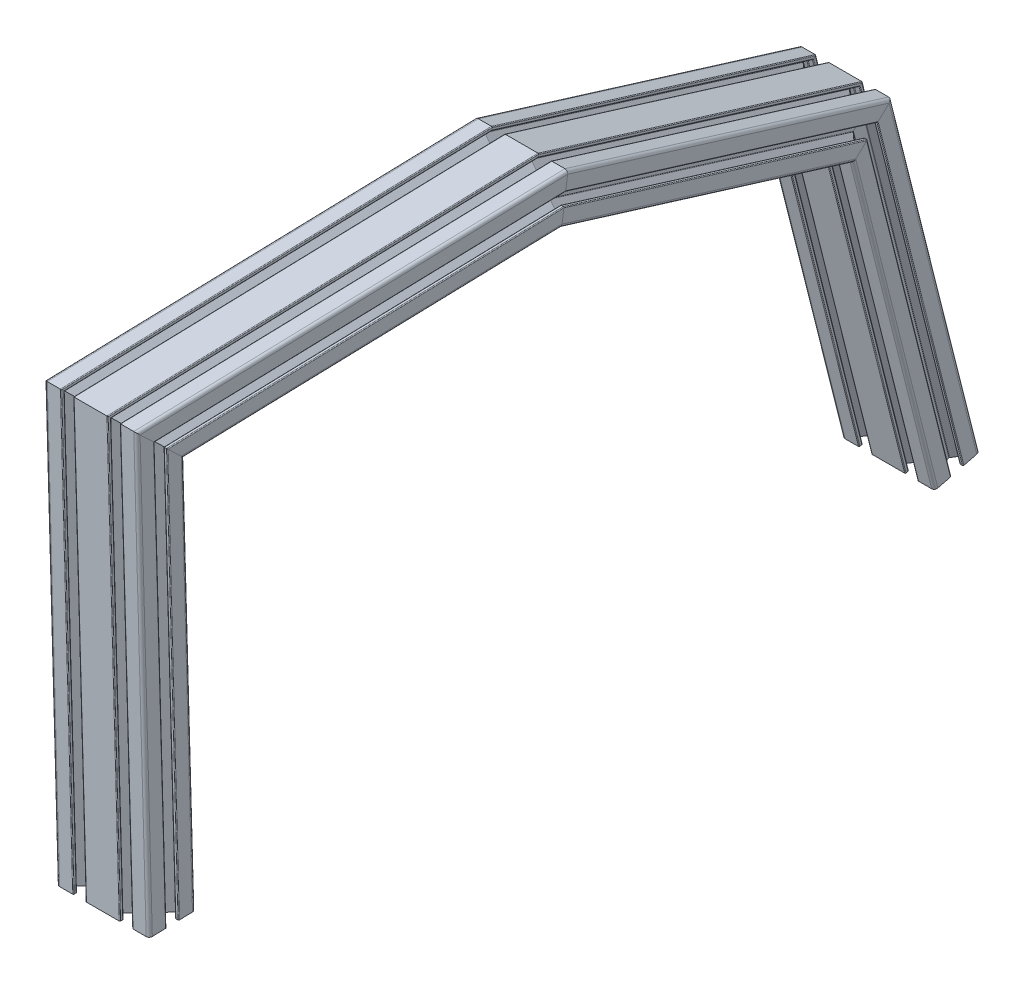
SolidWorks part; units mm, degrees
ref_plane "Front Plane" through (0, 0, 0) normal (0, 0, 1) x (1, 0, 0)
ref_plane "Top Plane" through (0, 0, 0) normal (0, 1, 0) x (1, 0, 0)
ref_plane "Right Plane" through (0, 0, 0) normal (1, 0, 0) x (0, 0, -1)
sketch "Sketch2" plane through (66.7101, 0, 48.5855) normal (0, 1, 0) x (1, 0, 0)
  line L1 (-190.5, -254) -> (190.5, -254)
  line L2 (-190.5, -254) -> (-190.5, 254)
  line L3 (-190.5, 254) -> (190.5, 254)
  line L4 (190.5, -254) -> (190.5, 254)
  line L5 (-190.5, -254) -> (190.5, 254) construction
  line L6 (-190.5, 254) -> (190.5, -254) construction
  point P0 (0, 0)
sketch "Sketch3" plane through (0, 0, 0) normal (0, 1, 0) x (1, 0, 0)
  line L0 (66.7101, -48.5855) -> (66.7101, -302.5855) construction
  line L1 (66.7101, -302.5855) -> (66.7101, 205.4145) construction
  line L2 (-123.7899, -302.5855) -> (257.2101, -302.5855) construction
  line L10 (-123.7899, 205.4145) -> (257.2101, 205.4145) construction
  point P3 (0, 0)
  point P7 (0, 0)
  point P8 (0, 0)
  point P9 (0, 0)
  point P13 (0, 0)
  point P14 (0, 0)
  point P16 (66.7101, 205.4145)
ref_plane "Plane1" through (66.7101, 0, 0) normal (1, 0, 0) x (0, 0, -1)
sketch "Sketch5" plane through (66.7101, 0, 0) normal (1, 0, 0) x (0, 0, -1)
  line L0 (-48.5855, 0) -> (-48.5855, 279.4) construction
  line L1 (-302.5855, 0) -> (-310.1662, 272.1127)
  line L2 (-302.5855, 0) -> (205.4145, 0) construction
  line L3 (-302.5855, 0) -> (205.4145, 0) construction
  line L4 (-310.1662, 272.1127) -> (-48.5855, 279.4)
  line L5 (-48.5855, 279.4) -> (150.4939, 218.0588)
  line L6 (150.4939, 218.0588) -> (205.4145, 0)
  point P10 (0, 0)
  point P28 (205.4145, 0)
  dimension "D1" = 279.4
other "8020 6030(1)" corner treatment miter
ref_plane "Plane2" through (66.7101, 0, 302.5855) normal (0, -0.9996, -0.0278) x (1, 0, 0)
sketch "Sketch21" plane through (66.7101, 0, 302.5855) normal (0, -0.9996, -0.0278) x (1, 0, 0)
  line L0 (11.1749, 2.3185) -> (11.9567, 1.3394) construction
  line L1 (13.6606, 3.0433) -> (12.6815, 3.8251) construction
  line L2 (-4.55, 12.3) -> (-4.55, 9.2682)
  line L3 (4.05, 12.8) -> (-4.05, 12.8)
  line L4 (4.55, 9.2682) -> (4.55, 12.3)
  line L5 (9.0188, 4.178) -> (4.9893, 8.2075)
  line L6 (9.1653, 0.8875) -> (9.1653, 3.8245)
  line L7 (9.6753, -0.0625) -> (9.1653, 0.8875) construction
  line L8 (9.1653, -1.0125) -> (9.6753, -0.0625) construction
  line L9 (9.1653, -3.8245) -> (9.1653, -1.0125)
  line L10 (4.9893, -8.2075) -> (9.0188, -4.178)
  line L11 (4.55, -12.3) -> (4.55, -9.2682)
  line L12 (-4.05, -12.8) -> (4.05, -12.8)
  line L13 (-4.55, -9.2682) -> (-4.55, -12.3)
  line L14 (-9.0188, -4.178) -> (-4.9893, -8.2075)
  line L15 (-9.1653, -1.0125) -> (-9.1653, -3.8245)
  line L16 (-9.6753, -0.0625) -> (-9.1653, -1.0125) construction
  line L17 (-9.1653, 0.8875) -> (-9.6753, -0.0625) construction
  line L18 (-9.1653, 3.8245) -> (-9.1653, 0.8875)
  line L19 (-4.9893, 8.2075) -> (-9.0188, 4.178)
  line L20 (17.3185, 3.8251) -> (16.3393, 3.0433) construction
  line L21 (18.0433, 1.3394) -> (18.8251, 2.3185) construction
  line L22 (18.8251, -2.3185) -> (18.0433, -1.3394) construction
  line L23 (16.3393, -3.0433) -> (17.3185, -3.8251) construction
  line L24 (12.6856, -3.8343) -> (13.6707, -3.0477) construction
  line L25 (11.9608, -1.3486) -> (11.179, -2.3278) construction
  line L26 (-18.8251, 2.3185) -> (-18.0433, 1.3394) construction
  line L27 (-16.3393, 3.0433) -> (-17.3185, 3.8251) construction
  line L28 (-12.6815, 3.8251) -> (-13.6606, 3.0433) construction
  line L29 (-11.9567, 1.3394) -> (-11.1749, 2.3185) construction
  line L30 (-11.1749, -2.3185) -> (-11.9567, -1.3394) construction
  line L31 (-13.6606, -3.0433) -> (-12.6815, -3.8251) construction
  line L32 (-17.3144, -3.8343) -> (-16.3292, -3.0477) construction
  line L33 (-18.0392, -1.3486) -> (-18.821, -2.3278) construction
  line L34 (-24.5, 9.88) -> (-24.5, 13.319)
  line L35 (-28.3189, 9.5) -> (-24.88, 9.5)
  line L36 (-28.6999, 12.7) -> (-28.6999, 9.881)
  line L37 (-24.881, 13.7) -> (-27.6999, 13.7)
  line L38 (-7.2674, -12.7425) -> (-10.4375, -12.7425)
  line L39 (-10.9375, -13.2425) -> (-10.9375, -14.5)
  line L40 (-10.4375, -15) -> (10.4375, -15)
  line L41 (10.9375, -14.5) -> (10.9375, -13.2425)
  line L42 (10.4375, -12.7425) -> (7.2674, -12.7425)
  line L43 (6.75, -12.2428) -> (6.75, -10.2602)
  line L44 (6.8964, -9.9067) -> (10.822, -5.9811)
  line L45 (11.1755, -5.8347) -> (14.05, -5.8347)
  line L46 (14.05, -5.8347) -> (15, -5.3247) construction
  line L47 (15, -5.3247) -> (15.95, -5.8347) construction
  line L48 (15.95, -5.8347) -> (18.8244, -5.8347)
  line L49 (19.178, -5.9811) -> (23.1035, -9.9067)
  line L50 (23.25, -10.2602) -> (23.25, -12.2428)
  line L51 (22.7325, -12.7425) -> (19.4375, -12.7425)
  line L52 (18.9375, -13.2425) -> (18.9375, -14.5)
  line L53 (19.4375, -15) -> (27.9999, -15)
  line L54 (29.9999, -13) -> (29.9999, -4.5625)
  line L55 (29.4999, -4.0625) -> (28.2425, -4.0625)
  line L56 (27.7425, -4.5625) -> (27.7425, -7.7325)
  line L57 (27.2428, -8.25) -> (25.2602, -8.25)
  line L58 (24.9066, -8.1035) -> (20.9811, -4.178)
  line L59 (20.8347, -3.8245) -> (20.8347, -1.0125)
  line L60 (20.8347, -1.0125) -> (20.3247, -0.0625) construction
  line L61 (20.3247, -0.0625) -> (20.8347, 0.8875) construction
  line L62 (20.8347, 0.8875) -> (20.8347, 3.8245)
  line L63 (20.9811, 4.178) -> (24.9066, 8.1035)
  line L64 (25.2602, 8.25) -> (27.2428, 8.25)
  line L65 (27.7425, 7.7325) -> (27.7425, 4.4375)
  line L66 (28.2425, 3.9375) -> (29.4999, 3.9375)
  line L67 (29.9999, 4.4375) -> (29.9999, 13)
  line L68 (27.9999, 15) -> (19.5625, 15)
  line L69 (19.0625, 14.5) -> (19.0625, 13.2425)
  line L70 (19.5625, 12.7425) -> (22.7325, 12.7425)
  line L71 (23.25, 12.2428) -> (23.25, 10.2602)
  line L72 (23.1035, 9.9067) -> (19.178, 5.9811)
  line L73 (18.8244, 5.8347) -> (15.95, 5.8347)
  line L74 (15.95, 5.8347) -> (15, 5.3247) construction
  line L75 (15, 5.3247) -> (14.05, 5.8347) construction
  line L76 (14.05, 5.8347) -> (11.1755, 5.8347)
  line L77 (10.822, 5.9811) -> (6.8964, 9.9067)
  line L78 (6.75, 10.2602) -> (6.75, 12.2428)
  line L79 (7.2674, 12.7425) -> (10.5625, 12.7425)
  line L80 (11.0625, 13.2425) -> (11.0625, 14.5)
  line L81 (10.5625, 15) -> (-10.5625, 15)
  line L82 (-11.0625, 14.5) -> (-11.0625, 13.2425)
  line L83 (-10.5625, 12.7425) -> (-7.2674, 12.7425)
  line L84 (-6.75, 12.2428) -> (-6.75, 10.2602)
  line L85 (-6.8964, 9.9067) -> (-10.822, 5.9811)
  line L86 (-11.1755, 5.8347) -> (-14.05, 5.8347)
  line L87 (-14.05, 5.8347) -> (-15, 5.3247) construction
  line L88 (-15, 5.3247) -> (-15.95, 5.8347) construction
  line L89 (-15.95, 5.8347) -> (-18.8244, 5.8347)
  line L90 (-19.178, 5.9811) -> (-23.1035, 9.9067)
  line L91 (-23.25, 10.2602) -> (-23.25, 12.2428)
  line L92 (-22.7325, 12.7425) -> (-19.5625, 12.7425)
  line L93 (-19.0625, 13.2425) -> (-19.0625, 14.5)
  line L94 (-19.5625, 15) -> (-27.9999, 15)
  line L95 (-29.9999, 13) -> (-29.9999, 4.4375)
  line L96 (-29.4999, 3.9375) -> (-28.2425, 3.9375)
  line L97 (-27.7425, 4.4375) -> (-27.7425, 7.7325)
  line L98 (-27.2428, 8.25) -> (-25.2602, 8.25)
  line L99 (-24.9066, 8.1035) -> (-20.9811, 4.178)
  line L100 (-20.8347, 3.8245) -> (-20.8347, 0.8875)
  line L101 (-20.8347, 0.8875) -> (-20.3247, -0.0625) construction
  line L102 (-20.3247, -0.0625) -> (-20.8347, -1.0125) construction
  line L103 (-20.8347, -1.0125) -> (-20.8347, -3.8245)
  line L104 (-20.9811, -4.178) -> (-24.9066, -8.1035)
  line L105 (-25.2602, -8.25) -> (-27.2428, -8.25)
  line L106 (-27.7425, -7.7325) -> (-27.7425, -4.5625)
  line L107 (-28.2425, -4.0625) -> (-29.4999, -4.0625)
  line L108 (-29.9999, -4.5625) -> (-29.9999, -13)
  line L109 (-27.9999, -15) -> (-19.4375, -15)
  line L110 (-18.9375, -14.5) -> (-18.9375, -13.2425)
  line L111 (-19.4375, -12.7425) -> (-22.7325, -12.7425)
  line L112 (-23.25, -12.2428) -> (-23.25, -10.2602)
  line L113 (-23.1035, -9.9067) -> (-19.178, -5.9811)
  line L114 (-18.8244, -5.8347) -> (-15.95, -5.8347)
  line L115 (-15.95, -5.8347) -> (-15, -5.3247) construction
  line L116 (-15, -5.3247) -> (-14.05, -5.8347) construction
  line L117 (-14.05, -5.8347) -> (-11.1755, -5.8347)
  line L118 (-10.822, -5.9811) -> (-6.8964, -9.9067)
  line L119 (-6.75, -10.2602) -> (-6.75, -12.2428)
  line L120 (-24.88, -9.5) -> (-28.3189, -9.5)
  line L121 (-24.5, -13.319) -> (-24.5, -9.88)
  line L122 (-27.6999, -13.7) -> (-24.881, -13.7)
  line L123 (-28.6999, -9.881) -> (-28.6999, -12.7)
  line L124 (24.5, -9.88) -> (24.5, -13.319)
  line L125 (28.3189, -9.5) -> (24.88, -9.5)
  line L126 (28.6999, -12.7) -> (28.6999, -9.881)
  line L127 (24.881, -13.7) -> (27.6999, -13.7)
  line L128 (27.6999, 13.7) -> (24.881, 13.7)
  line L129 (28.6999, 9.881) -> (28.6999, 12.7)
  line L130 (24.88, 9.5) -> (28.3189, 9.5)
  line L131 (24.5, 13.319) -> (24.5, 9.88)
  line L132 (-14.05, 5.8347) -> (-15.95, 5.8347)
  line L133 (-20.8347, 0.8875) -> (-20.8347, -1.0125)
  line L134 (-15.95, -5.8347) -> (-14.05, -5.8347)
  line L135 (-9.1653, -1.0125) -> (-9.1653, 0.8875)
  line L136 (9.1653, 0.8875) -> (9.1653, -1.0125)
  line L137 (14.05, -5.8347) -> (15.95, -5.8347)
  line L138 (20.8347, -1.0125) -> (20.8347, 0.8875)
  line L139 (15.95, 5.8347) -> (14.05, 5.8347)
  arc A0 (-4.05, 12.8) -> (-4.55, 12.3) centre (-4.05, 12.3) ccw
  arc A1 (4.55, 12.3) -> (4.05, 12.8) centre (4.05, 12.3) ccw
  arc A2 (4.55, 9.2682) -> (4.9893, 8.2075) centre (6.05, 9.2682) ccw
  arc A3 (9.1653, 3.8245) -> (9.0188, 4.178) centre (8.6653, 3.8245) ccw
  arc A4 (9.0188, -4.178) -> (9.1653, -3.8245) centre (8.6653, -3.8245) ccw
  arc A5 (4.9893, -8.2075) -> (4.55, -9.2682) centre (6.05, -9.2682) ccw
  arc A6 (4.05, -12.8) -> (4.55, -12.3) centre (4.05, -12.3) ccw
  arc A7 (-4.55, -12.3) -> (-4.05, -12.8) centre (-4.05, -12.3) ccw
  arc A8 (-4.55, -9.2682) -> (-4.9893, -8.2075) centre (-6.05, -9.2682) ccw
  arc A9 (-9.1653, -3.8245) -> (-9.0188, -4.178) centre (-8.6653, -3.8245) ccw
  arc A10 (-9.0188, 4.178) -> (-9.1653, 3.8245) centre (-8.6653, 3.8245) ccw
  arc A11 (-4.9893, 8.2075) -> (-4.55, 9.2682) centre (-6.05, 9.2682) ccw
  arc A12 (12.6815, 3.8251) -> (11.1749, 2.3185) centre (12.0126, 2.9874) ccw construction
  arc A13 (16.3393, 3.0433) -> (13.6606, 3.0433) centre (15, 0) ccw construction
  arc A14 (18.8251, 2.3185) -> (17.3185, 3.8251) centre (17.9873, 2.9874) ccw construction
  arc A15 (18.0433, -1.3394) -> (18.0433, 1.3394) centre (15, 0) ccw construction
  arc A16 (17.3185, -3.8251) -> (18.8251, -2.3185) centre (17.9873, -2.9874) ccw construction
  arc A17 (13.6707, -3.0477) -> (16.3393, -3.0433) centre (15, 0) ccw construction
  arc A18 (11.179, -2.3278) -> (12.6856, -3.8343) centre (12.0167, -2.9966) ccw construction
  arc A19 (11.9567, 1.3394) -> (11.9608, -1.3486) centre (15, 0) ccw construction
  arc A20 (-17.3185, 3.8251) -> (-18.8251, 2.3185) centre (-17.9873, 2.9874) ccw construction
  arc A21 (-13.6606, 3.0433) -> (-16.3393, 3.0433) centre (-15, 0) ccw construction
  arc A22 (-11.1749, 2.3185) -> (-12.6815, 3.8251) centre (-12.0126, 2.9874) ccw construction
  arc A23 (-11.9567, -1.3394) -> (-11.9567, 1.3394) centre (-15, 0) ccw construction
  arc A24 (-12.6815, -3.8251) -> (-11.1749, -2.3185) centre (-12.0126, -2.9874) ccw construction
  arc A25 (-16.3292, -3.0477) -> (-13.6606, -3.0433) centre (-15, 0) ccw construction
  arc A26 (-18.821, -2.3278) -> (-17.3144, -3.8343) centre (-17.9833, -2.9966) ccw construction
  arc A27 (-18.0433, 1.3394) -> (-18.0392, -1.3486) centre (-15, 0) ccw construction
  arc A28 (-7.2674, -12.7425) -> (-6.75, -12.2428) centre (-7.25, -12.2428) ccw
  arc A29 (-10.4375, -12.7425) -> (-10.9375, -13.2425) centre (-10.4375, -13.2425) ccw
  arc A30 (-10.9375, -14.5) -> (-10.4375, -15) centre (-10.4375, -14.5) ccw
  arc A31 (10.4375, -15) -> (10.9375, -14.5) centre (10.4375, -14.5) ccw
  arc A32 (10.9375, -13.2425) -> (10.4375, -12.7425) centre (10.4375, -13.2425) ccw
  arc A33 (6.75, -12.2428) -> (7.2674, -12.7425) centre (7.25, -12.2428) ccw
  arc A34 (6.8964, -9.9067) -> (6.75, -10.2602) centre (7.25, -10.2602) ccw
  arc A35 (11.1755, -5.8347) -> (10.822, -5.9811) centre (11.1755, -6.3347) ccw
  arc A36 (19.178, -5.9811) -> (18.8244, -5.8347) centre (18.8244, -6.3347) ccw
  arc A37 (23.25, -10.2602) -> (23.1035, -9.9067) centre (22.75, -10.2602) ccw
  arc A38 (22.7325, -12.7425) -> (23.25, -12.2428) centre (22.75, -12.2428) ccw
  arc A39 (19.4375, -12.7425) -> (18.9375, -13.2425) centre (19.4375, -13.2425) ccw
  arc A40 (18.9375, -14.5) -> (19.4375, -15) centre (19.4375, -14.5) ccw
  arc A41 (27.9999, -15) -> (29.9999, -13) centre (27.9999, -13) ccw
  arc A42 (29.9999, -4.5625) -> (29.4999, -4.0625) centre (29.4999, -4.5625) ccw
  arc A43 (28.2425, -4.0625) -> (27.7425, -4.5625) centre (28.2425, -4.5625) ccw
  arc A44 (27.2428, -8.25) -> (27.7425, -7.7325) centre (27.2428, -7.75) ccw
  arc A45 (24.9066, -8.1035) -> (25.2602, -8.25) centre (25.2602, -7.75) ccw
  arc A46 (20.8347, -3.8245) -> (20.9811, -4.178) centre (21.3347, -3.8245) ccw
  arc A47 (20.9811, 4.178) -> (20.8347, 3.8245) centre (21.3347, 3.8245) ccw
  arc A48 (25.2602, 8.25) -> (24.9066, 8.1035) centre (25.2602, 7.75) ccw
  arc A49 (27.7425, 7.7325) -> (27.2428, 8.25) centre (27.2428, 7.75) ccw
  arc A50 (27.7425, 4.4375) -> (28.2425, 3.9375) centre (28.2425, 4.4375) ccw
  arc A51 (29.4999, 3.9375) -> (29.9999, 4.4375) centre (29.4999, 4.4375) ccw
  arc A52 (29.9999, 13) -> (27.9999, 15) centre (27.9999, 13) ccw
  arc A53 (19.5625, 15) -> (19.0625, 14.5) centre (19.5625, 14.5) ccw
  arc A54 (19.0625, 13.2425) -> (19.5625, 12.7425) centre (19.5625, 13.2425) ccw
  arc A55 (23.25, 12.2428) -> (22.7325, 12.7425) centre (22.75, 12.2428) ccw
  arc A56 (23.1035, 9.9067) -> (23.25, 10.2602) centre (22.75, 10.2602) ccw
  arc A57 (18.8244, 5.8347) -> (19.178, 5.9811) centre (18.8244, 6.3347) ccw
  arc A58 (10.822, 5.9811) -> (11.1755, 5.8347) centre (11.1755, 6.3347) ccw
  arc A59 (6.75, 10.2602) -> (6.8964, 9.9067) centre (7.25, 10.2602) ccw
  arc A60 (7.2674, 12.7425) -> (6.75, 12.2428) centre (7.25, 12.2428) ccw
  arc A61 (10.5625, 12.7425) -> (11.0625, 13.2425) centre (10.5625, 13.2425) ccw
  arc A62 (11.0625, 14.5) -> (10.5625, 15) centre (10.5625, 14.5) ccw
  arc A63 (-10.5625, 15) -> (-11.0625, 14.5) centre (-10.5625, 14.5) ccw
  arc A64 (-11.0625, 13.2425) -> (-10.5625, 12.7425) centre (-10.5625, 13.2425) ccw
  arc A65 (-6.75, 12.2428) -> (-7.2674, 12.7425) centre (-7.25, 12.2428) ccw
  arc A66 (-6.8964, 9.9067) -> (-6.75, 10.2602) centre (-7.25, 10.2602) ccw
  arc A67 (-11.1755, 5.8347) -> (-10.822, 5.9811) centre (-11.1755, 6.3347) ccw
  arc A68 (-19.178, 5.9811) -> (-18.8244, 5.8347) centre (-18.8244, 6.3347) ccw
  arc A69 (-23.25, 10.2602) -> (-23.1035, 9.9067) centre (-22.75, 10.2602) ccw
  arc A70 (-22.7325, 12.7425) -> (-23.25, 12.2428) centre (-22.75, 12.2428) ccw
  arc A71 (-19.5625, 12.7425) -> (-19.0625, 13.2425) centre (-19.5625, 13.2425) ccw
  arc A72 (-19.0625, 14.5) -> (-19.5625, 15) centre (-19.5625, 14.5) ccw
  arc A73 (-27.9999, 15) -> (-29.9999, 13) centre (-27.9999, 13) ccw
  arc A74 (-29.9999, 4.4375) -> (-29.4999, 3.9375) centre (-29.4999, 4.4375) ccw
  arc A75 (-28.2425, 3.9375) -> (-27.7425, 4.4375) centre (-28.2425, 4.4375) ccw
  arc A76 (-27.2428, 8.25) -> (-27.7425, 7.7325) centre (-27.2428, 7.75) ccw
  arc A77 (-24.9066, 8.1035) -> (-25.2602, 8.25) centre (-25.2602, 7.75) ccw
  arc A78 (-20.8347, 3.8245) -> (-20.9811, 4.178) centre (-21.3347, 3.8245) ccw
  arc A79 (-20.9811, -4.178) -> (-20.8347, -3.8245) centre (-21.3347, -3.8245) ccw
  arc A80 (-25.2602, -8.25) -> (-24.9066, -8.1035) centre (-25.2602, -7.75) ccw
  arc A81 (-27.7425, -7.7325) -> (-27.2428, -8.25) centre (-27.2428, -7.75) ccw
  arc A82 (-27.7425, -4.5625) -> (-28.2425, -4.0625) centre (-28.2425, -4.5625) ccw
  arc A83 (-29.4999, -4.0625) -> (-29.9999, -4.5625) centre (-29.4999, -4.5625) ccw
  arc A84 (-29.9999, -13) -> (-27.9999, -15) centre (-27.9999, -13) ccw
  arc A85 (-19.4375, -15) -> (-18.9375, -14.5) centre (-19.4375, -14.5) ccw
  arc A86 (-18.9375, -13.2425) -> (-19.4375, -12.7425) centre (-19.4375, -13.2425) ccw
  arc A87 (-23.25, -12.2428) -> (-22.7325, -12.7425) centre (-22.75, -12.2428) ccw
  arc A88 (-23.1035, -9.9067) -> (-23.25, -10.2602) centre (-22.75, -10.2602) ccw
  arc A89 (-18.8244, -5.8347) -> (-19.178, -5.9811) centre (-18.8244, -6.3347) ccw
  arc A90 (-10.822, -5.9811) -> (-11.1755, -5.8347) centre (-11.1755, -6.3347) ccw
  arc A91 (-6.75, -10.2602) -> (-6.8964, -9.9067) centre (-7.25, -10.2602) ccw
  arc A92 (-24.88, 9.5) -> (-24.5, 9.88) centre (-24.88, 9.88) ccw
  arc A93 (-28.6999, 9.881) -> (-28.3189, 9.5) centre (-28.3189, 9.881) ccw
  arc A94 (-27.6999, 13.7) -> (-28.6999, 12.7) centre (-27.6999, 12.7) ccw
  arc A95 (-24.5, 13.319) -> (-24.881, 13.7) centre (-24.881, 13.319) ccw
  arc A96 (-24.5, -9.88) -> (-24.88, -9.5) centre (-24.88, -9.88) ccw
  arc A97 (-24.881, -13.7) -> (-24.5, -13.319) centre (-24.881, -13.319) ccw
  arc A98 (-28.6999, -12.7) -> (-27.6999, -13.7) centre (-27.6999, -12.7) ccw
  arc A99 (-28.3189, -9.5) -> (-28.6999, -9.881) centre (-28.3189, -9.881) ccw
  arc A100 (24.88, -9.5) -> (24.5, -9.88) centre (24.88, -9.88) ccw
  arc A101 (28.6999, -9.881) -> (28.3189, -9.5) centre (28.3189, -9.881) ccw
  arc A102 (27.6999, -13.7) -> (28.6999, -12.7) centre (27.6999, -12.7) ccw
  arc A103 (24.5, -13.319) -> (24.881, -13.7) centre (24.881, -13.319) ccw
  arc A104 (28.6999, 12.7) -> (27.6999, 13.7) centre (27.6999, 12.7) ccw
  arc A105 (28.3189, 9.5) -> (28.6999, 9.881) centre (28.3189, 9.881) ccw
  arc A106 (24.5, 9.88) -> (24.88, 9.5) centre (24.88, 9.88) ccw
  arc A107 (24.881, 13.7) -> (24.5, 13.319) centre (24.881, 13.319) ccw
  circle A108 centre (-15, 0) radius 3.325
  circle A109 centre (15, 0) radius 3.325
  point P350 (0, 0)
